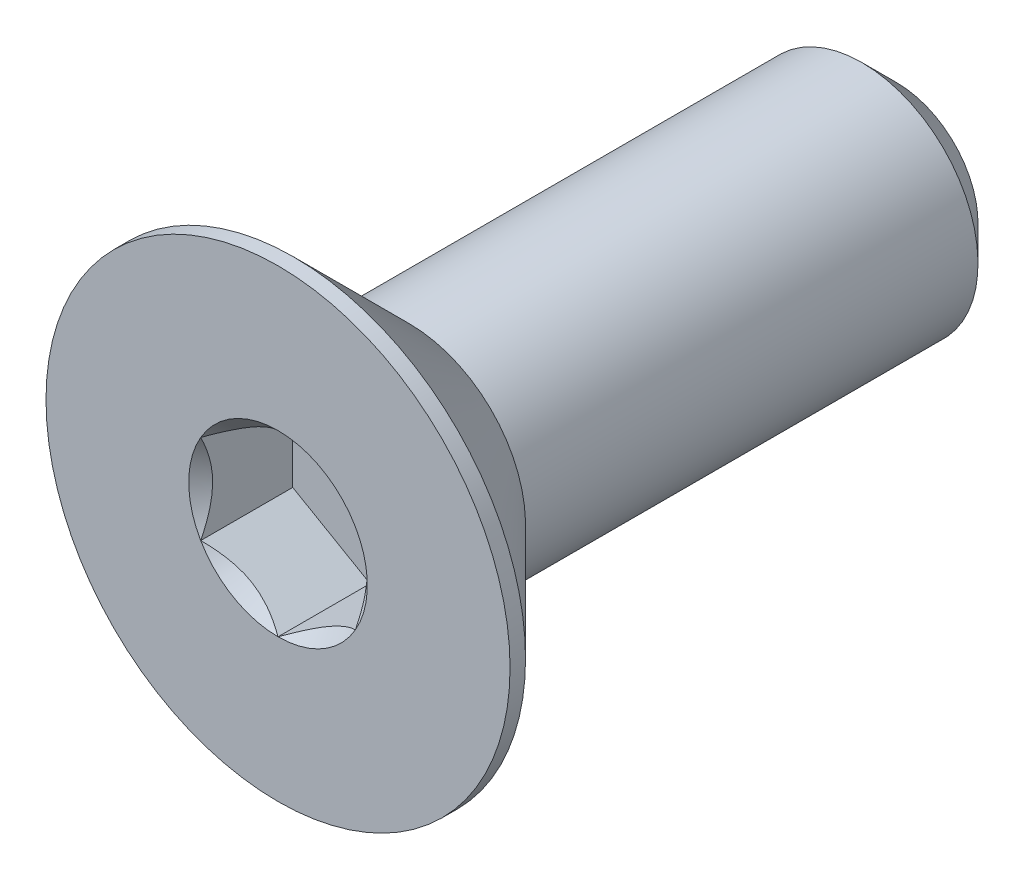
SolidWorks part; units mm, degrees
material "Alloy Steel"
ref_plane "Front" through (0, 0, 0) normal (0, 0, 1) x (1, 0, 0)
ref_plane "Top" through (0, 0, 0) normal (0, 1, 0) x (1, 0, 0)
ref_plane "Right" through (0, 0, 0) normal (1, 0, 0) x (0, 0, -1)
sketch "Sketch1" plane through (0, 0, 0) normal (1, 0, 0) x (0, 0, -1)
  line L0 (-4, 3) -> (-3.8, 3) construction
  line L1 (-3.8, 3) -> (-2.3, 1.5) construction
  line L2 (-4, 1.5) -> (4, 1.5) construction
  line L3 (4, 1.5) -> (4, 0) construction
  line L4 (4, 0) -> (-4, 0) construction
  line L5 (-4, 0) -> (-4, 3) construction
  line L6 (-4, 3) -> (-4, -3) construction
  line L7 (4, 1.5) -> (4, -1.5) construction
  line L8 (-4, -3) -> (-3.8, -3) construction
  line L9 (-3.8, -3) -> (-2.3, -1.5) construction
  line L11 (-4, 1.5) -> (-4, 0) construction
  line L12 (-2.3, 1.5) -> (-2.3, 0) construction
  line L13 (3.9688, 1.5541) -> (4.2188, 1.1211) construction
  line L14 (4.2188, 1.1211) -> (4.4688, 1.5541) construction
  line L15 (4.4688, 1.5541) -> (3.9688, 1.5541) construction
  line L16 (4.2188, 1.5541) -> (4.2188, 1.5) construction
  line L17 (4.2188, 1.5) -> (4.2188, 1.1752) construction
  line L18 (4.2188, 1.1752) -> (4.2188, 1.1211) construction
  line L19 (4.2188, 1.5271) -> (4.4531, 1.5271) construction
  line L20 (4.2188, 1.5271) -> (3.9844, 1.5271) construction
  line L21 (4, 1.5) -> (4.4375, 1.5) construction
  line L22 (4.1875, 1.1752) -> (4.25, 1.1752) construction
  line L23 (4, -1.5) -> (-2.3, -1.5) construction
  point P10 (2.75, -1.5)
  point P24 (-2.3, 1.5)
  point P30 (0, 0)
  dimension "Head Diameter" = 6
  dimension "Head Height" = 1.7
  dimension "Length" = 8
  dimension "Countersink Angle" = 90
  dimension "Thread Pitch" = 0.5
  dimension "D2" = 0.0625
  dimension "Minimum Thread Length" = 6.3
  dimension "Thread Size" = 3
  dimension "D1" = 1.25
sketch "Sketch2" plane through (0, 0, 0) normal (0, 0, 1) x (1, 0, 0)
  line L1 (0, 1.1547) -> (-1, 0.5774) construction
  line L2 (-1, 0.5774) -> (-1, -0.5774) construction
  line L3 (-1, -0.5774) -> (0, -1.1547) construction
  line L4 (0, -1.1547) -> (1, -0.5774) construction
  line L5 (1, -0.5774) -> (1, 0.5774) construction
  line L6 (1, 0.5774) -> (0, 1.1547) construction
  circle A0 centre (0, 0) radius 1 construction
  dimension "Drive Size" = 2
sketch "Sketch3" plane through (0, 0, 0) normal (1, 0, 0) x (0, 0, -1)
  line L0 (-4, 1.5) -> (4, 1.5)
  line L1 (4, 1.5) -> (4, 0)
  line L2 (4, 0) -> (-4, 0)
  line L3 (-4, 0) -> (-4, 1.5)
revolve "Revolve1" add sketch "Sketch3" angle 360 about L4
chamfer "Chamfer1" distance 0.45 angle 45 1 edges at (0, 1.5, -4)
sketch "Sketch6" plane through (0, 0, 0) normal (1, 0, 0) x (0, 0, -1)
  line L0 (-4, 3) -> (-3.8, 3)
  line L1 (-3.8, 3) -> (-2.3, 1.5)
  line L2 (-2.3, 1.5) -> (-2.3, 0)
  line L3 (-2.3, 0) -> (-4, 0)
  line L4 (-4, 0) -> (-4, 3)
revolve "Revolve2" add sketch "Sketch6" angle 360 about L4
sketch "Sketch8" plane through (0, 0, 4) normal (0, 0, 1) x (1, 0, 0)
  line L0 (0, 1.1547) -> (-1, 0.5774) construction
  line L1 (1, 0.5774) -> (0, 1.1547) construction
  line L2 (1, -0.5774) -> (1, 0.5774) construction
  line L3 (0, -1.1547) -> (1, -0.5774) construction
  line L4 (-1, 0.5774) -> (-1, -0.5774) construction
  line L5 (-1, -0.5774) -> (0, -1.1547) construction
  line L6 (0, 1.1547) -> (-1, 0.5774)
  line L7 (1, 0.5774) -> (0, 1.1547)
  line L8 (1, -0.5774) -> (1, 0.5774)
  line L9 (0, -1.1547) -> (1, -0.5774)
  line L10 (-1, 0.5774) -> (-1, -0.5774)
  line L11 (-1, -0.5774) -> (0, -1.1547)
extrude "Cut-Extrude1" cut sketch "Sketch8" against normal blind 1.19
sketch "Sketch9" plane through (0, 0, 4) normal (0, 0, 1) x (1, 0, 0)
  circle A0 centre (0, 0) radius 1.1547
extrude "Cut-Extrude2" cut sketch "Sketch9" against normal up to next (1.19 mm away) draft 45
ref_plane "Plane1" [suppressed] through (0, 0, 2.3) normal (0, 0, 1) x (1, 0, 0)
split "Split1" [suppressed] bodies to split 124
sketch "Sketch4" [suppressed] plane through (0, 0, -4) normal (0, 0, -1) x (-1, 0, 0)
  circle A0 centre (0, 0) radius 1.5 construction
  circle A1 centre (0, 0) radius 1.5
curve "Helix/Spiral1" [suppressed] pitch 0.5 height 6.8 turns 13.6
sketch "Sketch10" [suppressed] plane through (0, 0, 0) normal (1, 0, 0) x (0, 0, -1)
  line L0 (3.9844, 1.5271) -> (4.4531, 1.5271)
  line L1 (4.4531, 1.5271) -> (4.25, 1.1752)
  line L2 (4.25, 1.1752) -> (4.1875, 1.1752)
  line L3 (4.1875, 1.1752) -> (3.9844, 1.5271)
sweep "Cut-Sweep1" [suppressed] cut profiles "Sketch10" path "Helix/Spiral1"
equation "\"D2@Sketch1\" = \"Thread Pitch@Sketch1\" / 8"
equation "\"D4@Helix/Spiral1\"=\"Thread Pitch@Sketch1\""
equation "\"D3@Helix/Spiral1\"=\"Minimum Thread Length@Sketch1\"+\"Thread Pitch@Sketch1\""
equation "\"D1@Chamfer1\"=\"Thread Size@Sketch1\"*.15"
equation "\"D1@Cut-Extrude1\"=\"Head Height@Sketch1\"*.7"
equation "\"D1@Sketch1\"=\"Thread Pitch@Sketch1\"*2.5"
